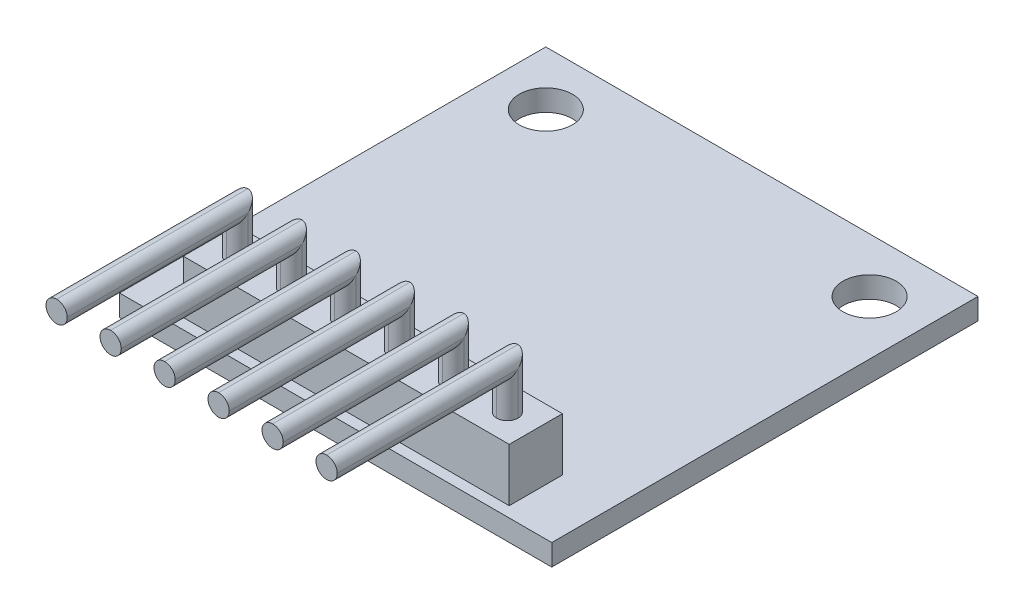
SolidWorks part; units mm, degrees
ref_plane "Front Plane" through (0, 0, 0) normal (0, 0, 1) x (1, 0, 0)
ref_plane "Top Plane" through (0, 0, 0) normal (0, 1, 0) x (1, 0, 0)
ref_plane "Right Plane" through (0, 0, 0) normal (1, 0, 0) x (0, 0, -1)
sketch "Sketch1" plane through (0, 0, 0) normal (0, 1, 0) x (1, 0, 0)
  line L0 (0, 0) -> (0, 4.9636) construction
  line L1 (-10.165, -10.025) -> (10.165, -10.025)
  line L2 (-10.165, -10.025) -> (-10.165, 10.025)
  line L3 (-10.165, 10.025) -> (10.165, 10.025)
  line L4 (10.165, -10.025) -> (10.165, 10.025)
  line L5 (-10.165, -10.025) -> (10.165, 10.025) construction
  line L6 (-10.165, 10.025) -> (10.165, -10.025) construction
  circle A0 centre (-7.615, 7.475) radius 1.25
  circle A1 centre (7.615, 7.475) radius 1.25
  point P0 (0, 0)
  dimension "D3" = 2.5
  dimension "D5" = 2.55
  dimension "D1" = 20.05
  dimension "D2" = 20.33
  dimension "D4" = 2.55
extrude "Boss-Extrude1" add sketch "Sketch1" along normal blind 1
sketch "Sketch2" plane through (0, 0, 0) normal (0, -1, 0) x (1, 0, 0)
  line L0 (10.165, -10.025) -> (-10.165, -10.025) construction
  line L1 (-4, 1.975) -> (4, 1.975)
  line L2 (-4, 1.975) -> (-4, 5.975)
  line L3 (-4, 5.975) -> (4, 5.975)
  line L4 (4, 1.975) -> (4, 5.975)
  line L5 (-4, 1.975) -> (4, 5.975) construction
  line L6 (-4, 5.975) -> (4, 1.975) construction
  point P0 (0, 3.975)
  point P7 (0, 0)
  dimension "D1" = 12
  dimension "D2" = 8
  dimension "D3" = 4
extrude "Boss-Extrude2" add sketch "Sketch2" along normal blind 1
sketch "Sketch3" plane through (0, 1, 0) normal (0, 1, 0) x (1, 0, 0)
  line L0 (-10.165, 10.025) -> (-10.165, -10.025) construction
  line L1 (-7.665, -7.025) -> (7.665, -7.025)
  line L2 (-7.665, -7.025) -> (-7.665, -9.525)
  line L3 (-7.665, -9.525) -> (7.665, -9.525)
  line L4 (7.665, -7.025) -> (7.665, -9.525)
  line L5 (10.165, -10.025) -> (10.165, 10.025) construction
  line L6 (-10.165, -10.025) -> (10.165, -10.025) construction
  dimension "D1" = 2.5
  dimension "D2" = 2.5
  dimension "D3" = 2.5
  dimension "D4" = 0.5
extrude "Boss-Extrude3" add sketch "Sketch3" along normal blind 2.5
sketch "Sketch4" plane through (0, 3.5, 0) normal (0, 1, 0) x (1, 0, 0)
  line L0 (-7.665, -7.025) -> (-7.665, -9.525) construction
  line L2 (-7.665, -9.525) -> (7.665, -9.525) construction
  line L3 (-6.895, -7.755) -> (-5.895, -7.755)
  line L4 (-6.895, -7.755) -> (-6.895, -8.755)
  line L5 (-6.895, -8.755) -> (-5.895, -8.755)
  line L6 (-5.895, -7.755) -> (-5.895, -8.755)
  dimension "D6" = 1
  dimension "D7" = 1
  dimension "D8" = 0.77
  dimension "D9" = 0.77
extrude "Boss-Extrude4" add sketch "Sketch4" along normal blind 2.5
sketch "Sketch5" plane through (0, 0, 8.755) normal (0, 0, 1) x (1, 0, 0)
  line L0 (-5.895, 6) -> (-5.895, 3.5) construction
  line L1 (-6.895, 6) -> (-5.895, 6)
  line L2 (-6.895, 6) -> (-6.895, 5)
  line L3 (-6.895, 5) -> (-5.895, 5)
  line L4 (-5.895, 6) -> (-5.895, 5)
  dimension "D1" = 1
extrude "Boss-Extrude5" add sketch "Sketch5" along normal blind 8
fillet "Fillet1" radius 0.5 8 edges at (-5.895, 5, 12.755) (-6.895, 5, 12.755) (-5.895, 4.25, 8.755) (-6.895, 4.25, 8.755) (-5.895, 4.75, 7.755) (-6.895, 4.75, 7.755) (-5.895, 6, 12.255) (-6.895, 6, 12.255)
pattern_linear "LPattern4" count 6 spacing 2.54 along (1, 0, 0) of "Fillet1", "Boss-Extrude5", "Boss-Extrude4"
